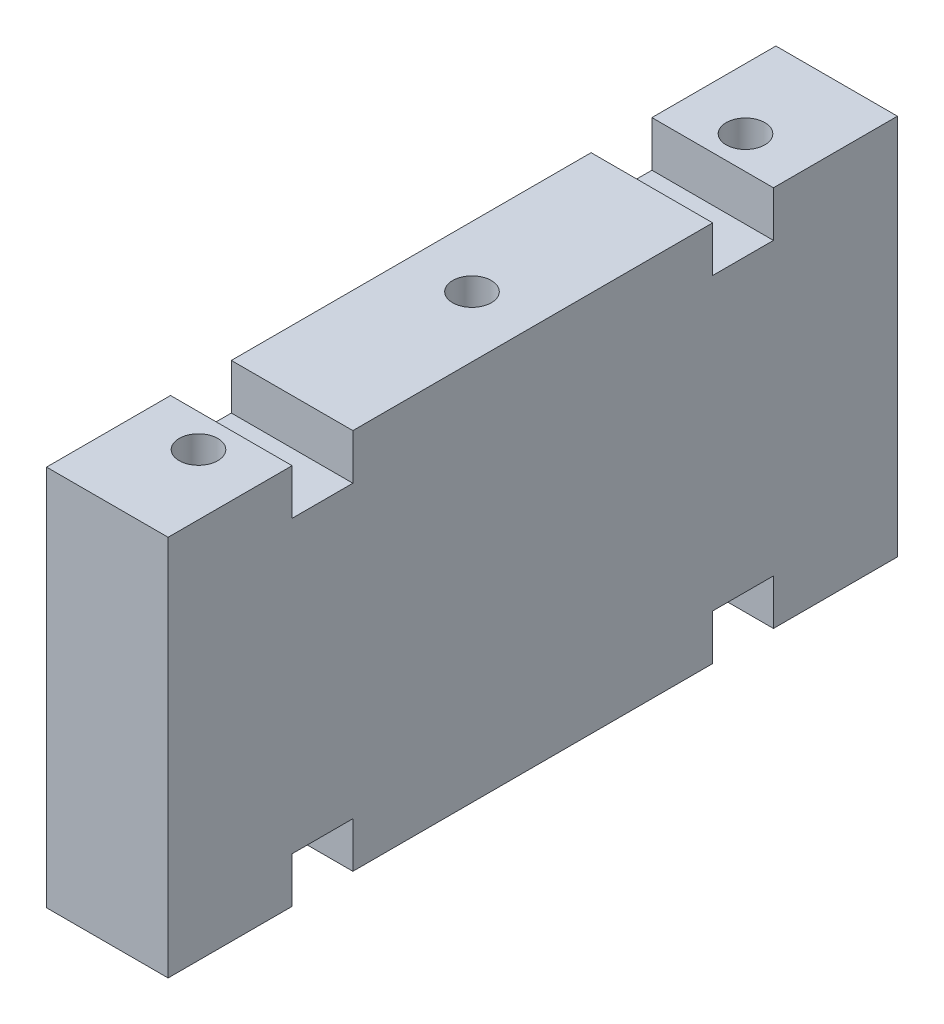
SolidWorks part; units mm, degrees
material "PET"
ref_plane "Front" through (0, 0, 0) normal (0, 0, 1) x (1, 0, 0)
ref_plane "Top" through (0, 0, 0) normal (0, 1, 0) x (1, 0, 0)
ref_plane "Right" through (0, 0, 0) normal (1, 0, 0) x (0, 0, -1)
sketch "Sketch1" plane through (0, 0, 0) normal (1, 0, 0) x (0, 0, -1)
  line L1 (-38.1, -19.939) -> (38.1, -19.939)
  line L2 (-38.1, -19.939) -> (-38.1, 19.939)
  line L3 (-38.1, 19.939) -> (38.1, 19.939)
  line L4 (38.1, -19.939) -> (38.1, 19.939)
  line L5 (-38.1, -19.939) -> (38.1, 19.939) construction
  line L6 (-38.1, 19.939) -> (38.1, -19.939) construction
  point P0 (0, 0)
  dimension "D1" = 39.878
  dimension "D2" = 76.2
extrude "Boss-Extrude1" add sketch "Sketch1" along normal blind 12.7
sketch "Sketch2" plane through (12.7, 0, 0) normal (1, 0, 0) x (0, 0, -1)
  line L0 (38.1, -19.939) -> (38.1, 19.939) construction
  line L1 (-25.146, 19.939) -> (-18.796, 19.939)
  line L2 (-25.146, 19.939) -> (-25.146, 15.1765)
  line L3 (-25.146, 15.1765) -> (-18.796, 15.1765)
  line L4 (-18.796, 19.939) -> (-18.796, 15.1765)
  line L5 (-25.146, 19.939) -> (-18.796, 15.1765) construction
  line L6 (-25.146, 15.1765) -> (-18.796, 19.939) construction
  line L7 (18.796, 19.939) -> (25.146, 19.939)
  line L8 (18.796, 19.939) -> (18.796, 15.1765)
  line L9 (18.796, 15.1765) -> (25.146, 15.1765)
  line L10 (25.146, 19.939) -> (25.146, 15.1765)
  line L11 (18.796, 19.939) -> (25.146, 15.1765) construction
  line L12 (18.796, 15.1765) -> (25.146, 19.939) construction
  line L13 (-25.146, -15.1765) -> (-18.796, -15.1765)
  line L14 (-25.146, -15.1765) -> (-25.146, -19.939)
  line L15 (-25.146, -19.939) -> (-18.796, -19.939)
  line L16 (-18.796, -15.1765) -> (-18.796, -19.939)
  line L17 (-25.146, -15.1765) -> (-18.796, -19.939) construction
  line L18 (-25.146, -19.939) -> (-18.796, -15.1765) construction
  line L19 (25.146, -19.939) -> (18.796, -19.939)
  line L20 (25.146, -19.939) -> (25.146, -15.1765)
  line L21 (25.146, -15.1765) -> (18.796, -15.1765)
  line L22 (18.796, -19.939) -> (18.796, -15.1765)
  line L23 (25.146, -19.939) -> (18.796, -15.1765) construction
  line L24 (25.146, -15.1765) -> (18.796, -19.939) construction
  line L27 (-38.1, 19.939) -> (-38.1, -19.939) construction
  line L29 (38.1, 19.939) -> (-38.1, 19.939) construction
  line L30 (-38.1, -19.939) -> (38.1, -19.939) construction
  point P0 (-21.971, 17.5578)
  point P5 (21.971, 17.5578)
  point P10 (-21.971, -17.5578)
  point P15 (21.971, -17.5578)
  dimension "D1" = 6.35
  dimension "D2" = 4.7625
  dimension "D3" = 12.954
  dimension "D6" = 12.954
extrude "Cut-Extrude1" cut sketch "Sketch2" against normal through all
sketch "Sketch5" plane through (0, 19.939, 0) normal (0, 1, 0) x (1, 0, 0)
  line L0 (12.7, -38.1) -> (0, -38.1) construction
  line L1 (12.7, 38.1) -> (0, 38.1) construction
  line L2 (6.35, -28.575) -> (6.35, 0) construction
  line L3 (6.35, 0) -> (6.35, 28.575) construction
  line L5 (6.35, 28.575) -> (0, 28.575) construction
  line L6 (0, 38.1) -> (0, 25.146) construction
  line L8 (6.35, 28.575) -> (12.7, 28.575) construction
  line L9 (12.7, 38.1) -> (12.7, 25.146) construction
  point P1 (6.35, 28.575)
  point P3 (6.35, 0)
  point P5 (6.35, -28.575)
  dimension "D1" = 9.525
  dimension "D2" = 9.525
hole_wizard "#10-32 Tapped Hole1" positions "Sketch5" profile "Sketch4" tap size "#10-32" standard "ANSI Inch" end condition up to next
sketch "Sketch4" plane through (6.35, 19.939, -28.575) normal (1, 0, 0) x (0, 0, 1)
  line L0 (0, 0) -> (0, 39.878)
  line L1 (0, 39.878) -> (2.0193, 39.878)
  line L2 (2.0193, 39.878) -> (2.0193, 0)
  line L5 (2.0193, 0) -> (0, 0)
  line L11 (0, -6.35) -> (0, 107.95) construction
  dimension "Thru Tap Drill Dia." = 4.0386
  dimension "Thru Tap Drill Depth" = 39.878
